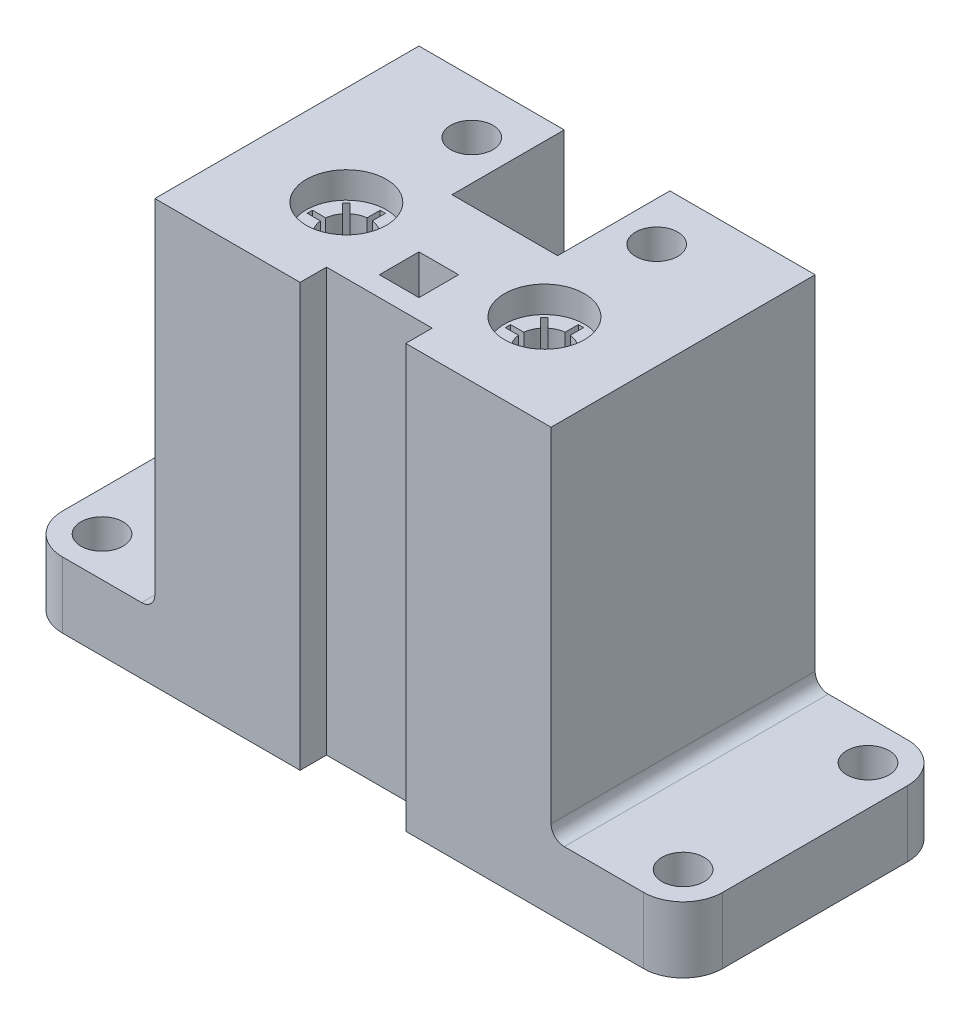
SolidWorks part; units mm, degrees
ref_plane "前视基准面" through (0, 0, 0) normal (0, 0, 1) x (1, 0, 0)
ref_plane "上视基准面" through (0, 0, 0) normal (0, 1, 0) x (1, 0, 0)
ref_plane "右视基准面" through (0, 0, 0) normal (1, 0, 0) x (0, 0, -1)
sketch "草图1" plane through (0, 0, 0) normal (0, 1, 0) x (1, 0, 0)
  line L1 (-15, -10) -> (15, -10)
  line L2 (-15, -10) -> (-15, 10)
  line L3 (-15, 10) -> (15, 10)
  line L4 (15, -10) -> (15, 10)
  line L5 (-15, -10) -> (15, 10) construction
  line L6 (-15, 10) -> (15, -10) construction
  point P0 (0, 0)
  dimension "D1" = 30
  dimension "D2" = 30
  dimension "D3" = 20
extrude "凸台-拉伸1" add sketch "草图1" along normal blind 32
sketch "草图2" plane through (0, 32, 0) normal (0, 1, 0) x (1, 0, 0)
  line L0 (-7.5, -3) -> (7.5, -3) construction
  line L1 (0, 0) -> (0, -3) construction
  line L2 (-15, -10) -> (15, -10) construction
  circle A0 centre (-7.5, -3) radius 1.775
  circle A1 centre (7.5, -3) radius 1.775
  dimension "D1" = 3.55
  dimension "D2" = 15
  dimension "D3" = 7
extrude "切除-拉伸1" cut sketch "草图2" against normal blind 4.5
sketch "草图3" plane through (0, 27.5, 0) normal (0, 1, 0) x (1, 0, 0)
  circle A1 centre (-7.5, -3) radius 1.775
  circle A2 centre (-7.5, -3) radius 1.775
  circle A3 centre (7.5, -3) radius 1.775
  circle A4 centre (7.5, -3) radius 1.775
  dimension "D1" = 0
  dimension "D2" = 0
extrude "切除-拉伸2" cut sketch "草图3" against normal blind 4.5 from offset 23 offset against normal yes
sketch "草图4" plane through (0, 32, 0) normal (0, 1, 0) x (1, 0, 0)
  line L0 (0, 0) -> (0, 10) construction
  line L1 (15, 10) -> (-15, 10) construction
  line L2 (7.5, -3) -> (-7.5, -3) construction
  line L3 (4, 1.5) -> (-4, 1.5)
  line L4 (4, 1.5) -> (4, 10)
  line L5 (4, 10) -> (-4, 10)
  line L6 (-4, 1.5) -> (-4, 10)
  line L7 (4, 1.5) -> (-4, 10) construction
  line L8 (4, 10) -> (-4, 1.5) construction
  circle A0 centre (7.5, -3) radius 1.775 construction
  circle A1 centre (7.5, -3) radius 1.775 construction
  circle A2 centre (-7.5, -3) radius 1.775 construction
  circle A3 centre (-7.5, -3) radius 1.775 construction
  point P5 (0, 5.75)
  dimension "D1" = 8
  dimension "D2" = 4.5
extrude "切除-拉伸3" cut sketch "草图4" against normal blind 25
sketch "草图6" plane through (0, 27.5, 0) normal (0, 1, 0) x (1, 0, 0)
  circle A0 centre (7.5, -3) radius 1.775 construction
  circle A1 centre (7.5, -3) radius 1.775 construction
  circle A2 centre (-7.5, -3) radius 1.775 construction
  circle A3 centre (-7.5, -3) radius 1.775 construction
  circle A4 centre (7.5, -3) radius 1.675
  circle A5 centre (-7.5, -3) radius 1.675
  dimension "D1" = 3.35
extrude "切除-拉伸5" cut sketch "草图6" against normal through all
sketch "草图5" plane through (0, 0, -10) normal (0, 0, -1) x (-1, 0, 0)
  line L0 (9.275, 27.5) -> (5.725, 27.5) construction
  line L1 (9.275, 27.5) -> (5.725, 27.5) construction
  line L2 (5.725, 4.5) -> (9.275, 4.5) construction
  line L3 (5.725, 4.5) -> (9.275, 4.5) construction
  line L4 (7.5, 27.5) -> (7.5, 4.5) construction
  line L5 (0, 0) -> (0, 37.272) construction
  line L6 (7, 24) -> (8, 24)
  line L7 (7, 24) -> (7, 8)
  line L8 (7, 8) -> (8, 8)
  line L9 (8, 24) -> (8, 8)
  line L10 (7, 24) -> (8, 8) construction
  line L11 (7, 8) -> (8, 24) construction
  line L12 (-7, 24) -> (-8, 24)
  line L13 (-7, 24) -> (-7, 8)
  line L14 (-7, 8) -> (-8, 8)
  line L15 (-8, 24) -> (-8, 8)
  point P6 (7.5, 16)
  dimension "D1" = 1
  dimension "D2" = 16
extrude "切除-拉伸4" cut sketch "草图5" against normal through all
sketch "草图7" plane through (0, 32, 0) normal (0, 1, 0) x (1, 0, 0)
  line L0 (0, 0) -> (0, -10) construction
  line L1 (-15, -10) -> (15, -10) construction
  line L3 (4, -8) -> (-4, -8)
  line L4 (4, -8) -> (4, -10)
  line L5 (4, -10) -> (-4, -10)
  line L6 (-4, -8) -> (-4, -10)
  line L7 (4, -8) -> (-4, -10) construction
  line L8 (4, -10) -> (-4, -8) construction
  point P5 (0, -9)
  dimension "D1" = 2
  dimension "D2" = 8
extrude "切除-拉伸6" cut sketch "草图7" against normal through all
sketch "草图8" plane through (0, 0, -10) normal (0, 0, -1) x (-1, 0, 0)
  line L0 (0, 0) -> (0, 32) construction
  line L1 (-15, 32) -> (-4, 32) construction
  line L2 (-15, 32) -> (-15, 0) construction
  line L3 (0, 16) -> (23.025, 16) construction
  line L4 (4, 32) -> (-4, 32) construction
  line L5 (4, 32) -> (-4, 32) construction
  circle A0 centre (-12, 29) radius 1.6
  circle A1 centre (12, 29) radius 1.6
  circle A2 centre (-12, 3) radius 1.6
  circle A3 centre (12, 3) radius 1.6
  dimension "D1" = 3.2
  dimension "D2" = 3
  dimension "D3" = 3
extrude "切除-拉伸7" cut sketch "草图8" against normal blind 6
sketch "草图9" plane through (0, 0, -10) normal (0, 0, -1) x (-1, 0, 0)
  line L0 (0, 0) -> (0, 9.7164) construction
  line L1 (-12.35, 2.65) -> (-9.65, 2.65)
  line L2 (-12.35, 2.65) -> (-12.35, 5.35)
  line L3 (-12.35, 5.35) -> (-9.65, 5.35)
  line L4 (-9.65, 2.65) -> (-9.65, 5.35)
  line L5 (-12.35, 2.65) -> (-9.65, 5.35) construction
  line L6 (-12.35, 5.35) -> (-9.65, 2.65) construction
  line L7 (-15, 0) -> (15, 0) construction
  line L8 (12.35, 2.65) -> (9.65, 2.65)
  line L9 (12.35, 2.65) -> (12.35, 5.35)
  line L10 (12.35, 5.35) -> (9.65, 5.35)
  line L11 (9.65, 2.65) -> (9.65, 5.35)
  line L12 (-15, 32) -> (-15, 0) construction
  point P0 (-11, 4)
  dimension "D1" = 4
  dimension "D2" = 4
  dimension "D3" = 2.7
  dimension "D4" = 2.7
extrude "凸台-拉伸2" [suppressed] add sketch "草图9" along normal blind 4
sketch "草图10" plane through (0, 32, 0) normal (0, 1, 0) x (1, 0, 0)
  line L0 (0, 0) -> (0, 16.0129) construction
  line L1 (13.6, 10) -> (10.4, 10) construction
  line L2 (15, -10) -> (15, 10) construction
  circle A0 centre (7, 6) radius 1.6
  circle A1 centre (-7, 6) radius 1.6
  dimension "D1" = 3.2
  dimension "D2" = 4
  dimension "D3" = 8
extrude "切除-拉伸8" cut sketch "草图10" against normal blind 6
chamfer "倒角1" distance 0.5 angle 45 4 edges at (7.5, 0, 4.775) (-7.5, 0, 4.775) (-7.5, 32, 4.775) (7.5, 32, 4.775)
sketch "草图11" plane through (0, 32, 0) normal (0, 1, 0) x (1, 0, 0)
  line L0 (7.5, -3) -> (2.5054, -3) construction
  line L2 (4.7363, -3.2) -> (5.7363, -3.2)
  line L3 (4.7363, -3.2) -> (4.7363, -2.8)
  line L4 (4.7363, -2.8) -> (5.7363, -2.8)
  line L5 (5.7363, -3.2) -> (5.7363, -2.8)
  line L6 (4.7363, -3.2) -> (5.7363, -2.8) construction
  line L7 (4.7363, -2.8) -> (5.7363, -3.2) construction
  circle A0 centre (7.5, -3) radius 1.775 construction
  circle A1 centre (7.5, -3) radius 1.775 construction
  point P3 (5.2363, -3)
  dimension "D1" = 0.4
  dimension "D2" = 1
extrude "切除-拉伸9" cut sketch "草图11" against normal up to surface (4.5 mm away) up to face at (7.5, 27.5, 4.675)
pattern_circular "阵列(圆周)1" count 8 over 360 about axis through (7.5, 27.5, 3) along (0, 1, 0) of "切除-拉伸9"
sketch "草图12" plane through (0, 0, 0) normal (0, -1, 0) x (1, 0, 0)
  line L0 (7.5, 3) -> (1.3987, 3) construction
  line L2 (4.7363, 2.8) -> (5.7363, 2.8)
  line L3 (4.7363, 2.8) -> (4.7363, 3.2)
  line L4 (4.7363, 3.2) -> (5.7363, 3.2)
  line L5 (5.7363, 2.8) -> (5.7363, 3.2)
  line L6 (4.7363, 2.8) -> (5.7363, 3.2) construction
  line L7 (4.7363, 3.2) -> (5.7363, 2.8) construction
  circle A0 centre (7.5, 3) radius 1.775 construction
  circle A1 centre (7.5, 3) radius 1.775 construction
  point P4 (5.2363, 3)
  dimension "D1" = 0.4
  dimension "D2" = 1
extrude "切除-拉伸10" cut sketch "草图12" against normal up to surface (4.5 mm away) up to face at (7.5, 4.5, 4.675)
pattern_circular "阵列(圆周)2" count 8 over 360 about axis through (7.5, 4.5, 3) along (0, 1, 0) of "切除-拉伸10"
mirror "镜向1" about plane through (0, 0, 0) normal (1, 0, 0) of "阵列(圆周)2", "阵列(圆周)1"
sketch "草图13" plane through (0, 32, 0) normal (0, 1, 0) x (1, 0, 0)
  line L0 (0, 0) -> (0, -5) construction
  line L1 (4, -10) -> (15, -10) construction
  line L2 (-1.5, -6.5) -> (1.5, -6.5)
  line L3 (-1.5, -6.5) -> (-1.5, -3.5)
  line L4 (-1.5, -3.5) -> (1.5, -3.5)
  line L5 (1.5, -6.5) -> (1.5, -3.5)
  line L6 (-1.5, -6.5) -> (1.5, -3.5) construction
  line L7 (-1.5, -3.5) -> (1.5, -6.5) construction
  dimension "D1" = 3
  dimension "D2" = 3
  dimension "D3" = 5
extrude "切除-拉伸11" cut sketch "草图13" against normal blind 4
sketch "草图14" plane through (0, 0, 0) normal (0, -1, 0) x (1, 0, 0)
  line L0 (15, -10) -> (-15, -10) construction
  line L1 (15, 10) -> (25, 10)
  line L2 (15, 10) -> (15, -10)
  line L3 (15, -10) -> (25, -10)
  line L4 (25, 10) -> (25, -10)
  line L5 (0, 0) -> (0, -16.1877) construction
  dimension "D1" = 10
extrude "凸台-拉伸3" add sketch "草图14" against normal blind 5
sketch "草图15" plane through (0, 5, 0) normal (0, 1, 0) x (1, 0, 0)
  line L0 (22, 10) -> (22, -10) construction
  line L1 (15, 10) -> (25, 10) construction
  line L2 (25, -10) -> (15, -10) construction
  line L3 (25, 0) -> (32.2189, 0) construction
  line L4 (25, 10) -> (25, -10) construction
  circle A0 centre (22, 7) radius 1.6
  circle A1 centre (22, -7) radius 1.6
  dimension "D1" = 3.2
  dimension "D2" = 14
  dimension "D3" = 3
extrude "切除-拉伸12" cut sketch "草图15" against normal through all
mirror "镜向6" about plane through (0, 0, 0) normal (1, 0, 0) of "切除-拉伸12", "凸台-拉伸3"
fillet "圆角1" radius 1 2 edges at (15, 5, 0) (-15, 5, 0)
fillet "圆角2" radius 3 4 edges at (25, 2.5, -10) (25, 2.5, 10) (-25, 2.5, 10) (-25, 2.5, -10)
sketch "草图16" plane through (0, 32, 0) normal (0, 1, 0) x (1, 0, 0)
  line L0 (0, 0) -> (0, -11.4833) construction
  circle A0 centre (-7.5, -3) radius 1.675 construction
  circle A1 centre (-7.5, -3) radius 1.675 construction
  circle A2 centre (-7.5, -3) radius 3.025
  circle A3 centre (7.5, -3) radius 3.025
  dimension "D1" = 6.05
extrude "切除-拉伸13" cut sketch "草图16" against normal blind 2
ref_plane "基准面1" through (0, 16, 0) normal (0, 1, 0) x (1, 0, 0)
mirror "镜向7" about plane through (0, 16, 0) normal (0, 1, 0) of "切除-拉伸13"
sketch "草图17" plane through (0, 8, 0) normal (0, 1, 0) x (1, 0, 0)
  line L3 (-7, -1.4014) -> (-7, 10)
  line L4 (-7, 10) -> (-8, 10)
  line L5 (-8, 10) -> (-8, -1.4014)
  line L6 (-7, -1.4014) -> (-7, 10)
  line L7 (-7, 10) -> (-8, 10)
  line L8 (-8, 10) -> (-8, -1.4014)
  line L9 (8, -1.4014) -> (8, 10)
  line L10 (8, 10) -> (7, 10)
  line L11 (7, 10) -> (7, -1.4014)
  line L12 (8, -1.4014) -> (8, 10)
  line L13 (8, 10) -> (7, 10)
  line L14 (7, 10) -> (7, -1.4014)
  line L15 (-8, -4.5986) -> (-8, -10)
  line L16 (-8, -10) -> (-7, -10)
  line L17 (-7, -10) -> (-7, -4.5986)
  line L18 (-8, -4.5986) -> (-8, -10)
  line L19 (-8, -10) -> (-7, -10)
  line L20 (-7, -10) -> (-7, -4.5986)
  line L21 (7, -4.5986) -> (7, -10)
  line L22 (7, -10) -> (8, -10)
  line L23 (8, -10) -> (8, -4.5986)
  line L24 (7, -4.5986) -> (7, -10)
  line L25 (7, -10) -> (8, -10)
  line L26 (8, -10) -> (8, -4.5986)
  arc A1 (-7, -1.4014) -> (-8, -1.4014) centre (-7.5, -3) ccw
  arc A2 (-7, -1.4014) -> (-8, -1.4014) centre (-7.5, -3) ccw
  arc A3 (8, -1.4014) -> (7, -1.4014) centre (7.5, -3) ccw
  arc A4 (8, -1.4014) -> (7, -1.4014) centre (7.5, -3) ccw
  arc A5 (-8, -4.5986) -> (-7, -4.5986) centre (-7.5, -3) ccw
  arc A6 (-8, -4.5986) -> (-7, -4.5986) centre (-7.5, -3) ccw
  arc A7 (7, -4.5986) -> (8, -4.5986) centre (7.5, -3) ccw
  arc A8 (7, -4.5986) -> (8, -4.5986) centre (7.5, -3) ccw
  dimension "D1" = 0
  dimension "D2" = 0
  dimension "D3" = 0
  dimension "D4" = 0
extrude "凸台-拉伸4" add sketch "草图17" along normal up to next
